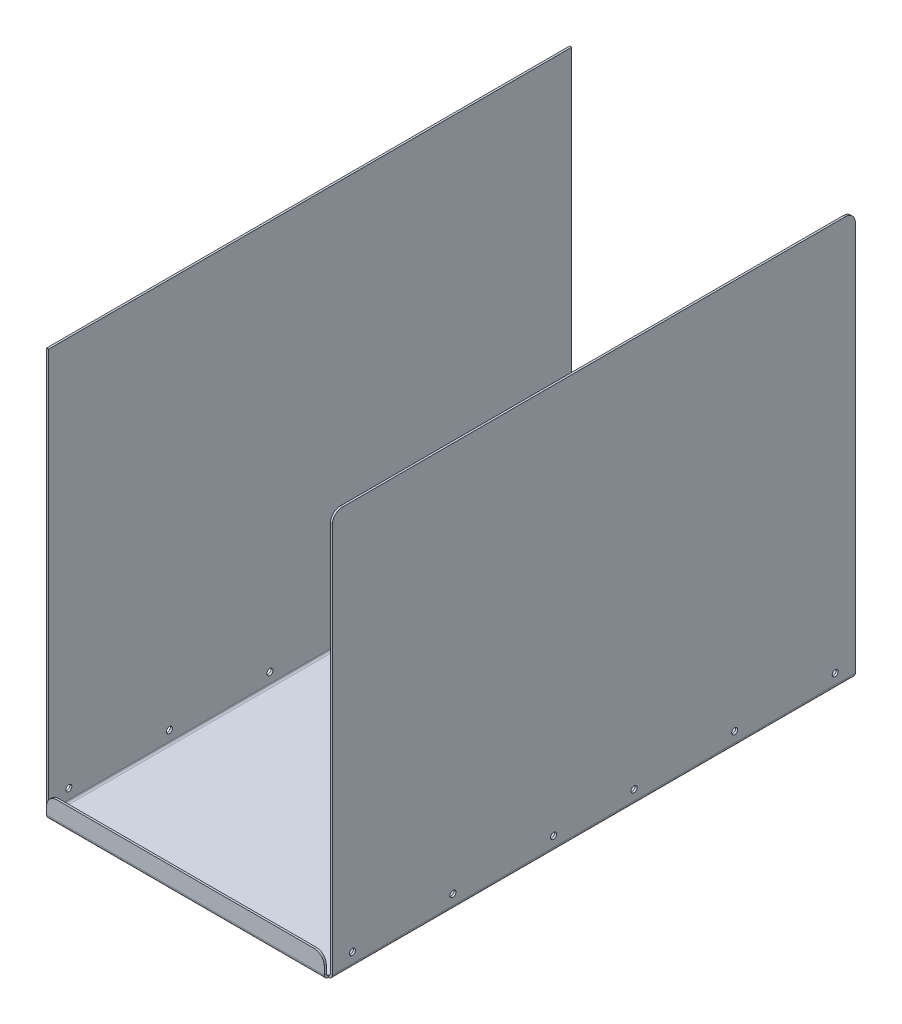
SolidWorks part; units mm, degrees
note: The reader was unsure of these and kept them because the rebuilt part matched: flange length of "Edge-Flange1", "Edge-Flange2", "Edge-Flange4", "Edge-Flange5".
material "AISI 1020"
ref_plane "Front Plane" through (0, 0, 0) normal (0, 0, 1) x (1, 0, 0)
ref_plane "Top Plane" through (0, 0, 0) normal (0, 1, 0) x (1, 0, 0)
ref_plane "Right Plane" through (0, 0, 0) normal (1, 0, 0) x (0, 0, -1)
sketch "Sketch1" plane through (0, 0, 0) normal (0, 1, 0) x (1, 0, 0)
  line L1 (0, 0) -> (142, 0)
  line L10 (0, 0) -> (0, 260)
  line L11 (0, 260) -> (142, 260)
  line L12 (142, 0) -> (142, 260)
  point P1 (142, 3.7794)
  point P2 (0, 0)
  point P5 (0, 0)
  point P6 (0, 0)
  point P7 (0, 0)
  point P9 (0, 0)
  point P18 (0, 3.1751)
  dimension "D1" = 260
  dimension "D2" = 142
base flange "Base-Flange1" sketch "Sketch1" thickness 1 reverse thickness direction no parameters "D1"=1
edge flange "Edge-Flange1" sketch "Sketch26" flange angle 90 flange length 201 flange position material inside bend radius 1 thickness 1 relief rectangular parameters "D6"=10
bend "EdgeBend7" bend radius 1 bend angle 90 parameters "D5"=1
sketch "Sketch26" plane through (0, 0, 0) normal (-1, 0, 0) x (0, 0, 1)
  line L0 (-260, 0) -> (0, 0) construction
  line L1 (-260, 0) -> (0, 0)
  line L2 (-260, 0) -> (-260, 200)
  line L3 (-260, 200) -> (0, 200)
  line L4 (0, 200) -> (0, 0)
  dimension "D1" = 200
edge flange "Edge-Flange2" sketch "Sketch28" flange angle 90 flange length 201 flange position material inside bend radius 1 thickness 1 relief rectangular parameters "D6"=10
bend "EdgeBend8" bend radius 1 bend angle 90 parameters "D5"=2
sketch "Sketch28" plane through (142, 0, 0) normal (1, 0, 0) x (0, 0, -1)
  line L0 (0, 0) -> (260, 0) construction
  line L1 (0, 0) -> (260, 0)
  line L2 (0, 0) -> (0, 195)
  line L3 (5, 200) -> (255, 200)
  line L4 (260, 195) -> (260, 0)
  arc A0 (255, 200) -> (260, 195) centre (255, 195) cw
  arc A1 (0, 195) -> (5, 200) centre (5, 195) cw
  point P8 (0, 200)
  dimension "D2" = 5
  dimension "D1" = 200
edge flange "Edge-Flange4" sketch "Sketch30" flange angle 90 flange length 11 flange position bend outside bend radius 1 thickness 1 relief rectangular parameters "D6"=10
bend "EdgeBend9" bend radius 1 bend angle 90 parameters "D5"=3
sketch "Sketch30" plane through (0, 0, -260) normal (0, 0, -1) x (-1, 0, 0)
  line L0 (-140, 0) -> (-2, 0) construction
  line L1 (-140, 0) -> (-2, 0)
  line L2 (-140, 0) -> (-140, 5)
  line L3 (-135, 10) -> (-7, 10)
  line L4 (-2, 5) -> (-2, 0)
  arc A0 (-7, 10) -> (-2, 5) centre (-7, 5) cw
  arc A1 (-140, 5) -> (-135, 10) centre (-135, 5) cw
  dimension "D2" = 5
  dimension "D1" = 10
sketch "Sketch12" plane through (0, 0, 0) normal (-1, 0, 0) x (0, 0, 1)
  line L0 (11.607, 6) -> (3.0829, 6) construction
  line L3 (11.607, 6) -> (-277.8535, 6) construction
  line L4 (0, 1) -> (0, 200) construction
  line L8 (0, 1) -> (-260, 1) construction
  circle A0 centre (-110, 6) radius 1.5
  circle A1 centre (-60, 6) radius 1.5
  circle A2 centre (-10, 6) radius 1.5
  circle A3 centre (-150, 6) radius 1.5
  circle A4 centre (-200, 6) radius 1.5
  circle A5 centre (-250, 6) radius 1.5
  point P12 (0, 5)
  point P13 (0, 0)
  point P22 (0, 0)
  point P25 (-277.8535, 5)
  point P26 (-250, 5)
  point P27 (-200, 5)
  point P28 (-128.6786, 5)
  point P29 (3.0829, 5)
  point P30 (-110, 5)
  point P31 (0, 0)
  point P32 (11.607, 5)
  point P33 (-10, 5)
  dimension "D1" = 3
  dimension "D2" = 3
  dimension "D3" = 3
  dimension "D4" = 10
  dimension "D5" = 50
  dimension "D7" = 3
  dimension "D8" = 3
  dimension "D9" = 3
  dimension "D10" = 40
  dimension "D11" = 50
  dimension "D12" = 50
  dimension "D6" = 50
  dimension "D13" = 5
extrude "Cut-Extrude1" cut sketch "Sketch12" along direction (-1, 0, 0) on the side against the normal blind 157 normal cut yes
edge flange "Edge-Flange5" sketch "Sketch32" flange angle 90 flange length 11 flange position bend outside bend radius 1 thickness 1 relief rectangular parameters "D6"=10
bend "EdgeBend10" bend radius 1 bend angle 90 parameters "D5"=4
sketch "Sketch32" plane through (0, 0, 0) normal (0, 0, 1) x (1, 0, 0)
  line L0 (2, 0) -> (140, 0) construction
  line L1 (2, 0) -> (140, 0)
  line L2 (2, 0) -> (2, 5)
  line L3 (7, 10) -> (135, 10)
  line L4 (140, 5) -> (140, 0)
  arc A0 (135, 10) -> (140, 5) centre (135, 5) cw
  arc A1 (2, 5) -> (7, 10) centre (7, 5) cw
  dimension "D1" = 5
sketch "Bend-Lines1" [suppressed] plane through (0, 0, 0) normal (0, 1, 0) x (1, 0, 0)
sketch "Bounding-Box1" [suppressed] plane through (0, 0, 0) normal (0, 1, 0) x (1, 0, 0)
sheet metal parameters "Sheet-Metal1" thickness 1 parameters "D1"=1
flat pattern "Flat-Pattern1" [suppressed]
sketch "Bend-Lines2" plane through (0, 0, 0) normal (0, 1, 0) x (1, 0, 0)
sketch3d "Bounding-Box2" [suppressed]
  line L0 (-142, 120, 0) -> (0, 120, 0) construction
  line L1 (-142, 0, 0) -> (0, 0, 0) construction
  line L2 (-142, 120, 0) -> (-142, 0, 0) construction
  line L3 (0, 120, 0) -> (0, 0, 0) construction
sheet metal parameters "Sheet-Metal2" thickness 1 parameters "D1"=1
flat pattern "Flat-Pattern1" [suppressed]
sketch "Bend-Lines2" plane through (0, 0, 0) normal (0, 1, 0) x (1, 0, 0)
  line L0 (141.1781, 0) -> (141.1781, 120) construction
  line L1 (141.1781, 0) -> (141.1781, 120) construction
sketch3d "Bounding-Box2" [suppressed]
  line L0 (0, 120, 0) -> (151.3562, 120, 0) construction
  line L1 (0, 0, 0) -> (151.3562, 0, 0) construction
  line L2 (0, 120, 0) -> (0, 0, 0) construction
  line L3 (151.3562, 120, 0) -> (151.3562, 0, 0) construction
bend of the flat pattern "Flatten-<EdgeBend7>1"
sheet metal parameters "Sheet-Metal3" thickness 1 parameters "D1"=1
flat pattern "Flat-Pattern1" [suppressed]
sketch "Bend-Lines2" plane through (0, 0, 0) normal (0, 1, 0) x (1, 0, 0)
  line L0 (141.1781, 0) -> (141.1781, 120) construction
  line L1 (141.1781, 0) -> (141.1781, 120) construction
  line L2 (0.8219, 120) -> (0.8219, 0) construction
  line L3 (0.8219, 120) -> (0.8219, 0) construction
sketch3d "Bounding-Box2" [suppressed]
  line L0 (151.3562, 0, 0) -> (151.3562, 280, 0) construction
  line L1 (-9.3562, 0, 0) -> (-9.3562, 280, 0) construction
  line L2 (151.3562, 0, 0) -> (-9.3562, 0, 0) construction
  line L3 (151.3562, 280, 0) -> (-9.3562, 280, 0) construction
bend of the flat pattern "Flatten-<EdgeBend7>5"
bend of the flat pattern "Flatten-<EdgeBend8>1"
sheet metal parameters "Sheet-Metal4" thickness 1 parameters "D1"=1
flat pattern "Flat-Pattern1" [suppressed]
sketch "Bend-Lines2" plane through (0, 0, 0) normal (0, 1, 0) x (1, 0, 0)
  line L0 (141.1781, 0) -> (141.1781, 120) construction
  line L1 (141.1781, 0) -> (141.1781, 120) construction
  line L2 (0.8219, 120) -> (0.8219, 0) construction
  line L3 (0.8219, 120) -> (0.8219, 0) construction
  line L4 (0.8219, 260) -> (0.8219, 140) construction
  line L5 (141.1781, 140) -> (141.1781, 260) construction
  line L6 (0.8219, 260) -> (0.8219, 140) construction
  line L7 (141.1781, 140) -> (141.1781, 260) construction
sketch3d "Bounding-Box2" [suppressed]
  line L0 (138.3563, 137.9999, 0) -> (138.3562, -122, 0) construction
  line L1 (-22.3561, 138, 0) -> (-22.3562, -121.9999, 0) construction
  line L2 (138.3563, 137.9999, 0) -> (-22.3561, 138, 0) construction
  line L3 (138.3562, -122, 0) -> (-22.3562, -121.9999, 0) construction
bend of the flat pattern "Flatten-<EdgeBend7>7"
bend of the flat pattern "Flatten-<EdgeBend8>5"
bend of the flat pattern "Flatten-<EdgeBend9>4"
sheet metal parameters "Sheet-Metal6" thickness 1 parameters "D1"=1
flat pattern "Flat-Pattern1" [suppressed]
sketch "Bend-Lines2" plane through (0, 0, 0) normal (0, 1, 0) x (1, 0, 0)
  line L0 (141.1781, 0) -> (141.1781, 120) construction
  line L1 (141.1781, 0) -> (141.1781, 120) construction
  line L2 (0.8219, 120) -> (0.8219, 0) construction
  line L3 (0.8219, 120) -> (0.8219, 0) construction
  line L4 (141.1781, 160) -> (141.1781, 280) construction
  line L5 (141.1781, 160) -> (141.1781, 280) construction
  line L6 (0.8219, 280) -> (0.8219, 160) construction
  line L7 (0.8219, 280) -> (0.8219, 160) construction
sketch3d "Bounding-Box2" [suppressed]
  line L0 (151.3562, 0, 0) -> (151.3562, 280, 0) construction
  line L1 (-9.3562, 0, 0) -> (-9.3562, 280, 0) construction
  line L2 (151.3562, 0, 0) -> (-9.3562, 0, 0) construction
  line L3 (151.3562, 280, 0) -> (-9.3562, 280, 0) construction
bend of the flat pattern "Flatten-<EdgeBend7>6"
bend of the flat pattern "Flatten-<EdgeBend8>4"
bend of the flat pattern "Flatten-<EdgeBend9>1"
sheet metal parameters "Sheet-Metal7" thickness 1 parameters "D1"=1
flat pattern "Flat-Pattern1"
sketch "Bend-Lines2" plane through (0, 0, 0) normal (0, 1, 0) x (1, 0, 0)
  line L10 (2, -1.1781) -> (140, -1.1781) construction
  line L11 (140, 261.1781) -> (2, 261.1781) construction
  line L12 (141.1781, 0) -> (141.1781, 260) construction
  line L13 (0.8219, 260) -> (0.8219, 0) construction
  line L14 (2, -1.1781) -> (140, -1.1781) construction
  line L15 (140, 261.1781) -> (2, 261.1781) construction
  line L16 (141.1781, 0) -> (141.1781, 260) construction
  line L17 (0.8219, 260) -> (0.8219, 0) construction
sketch3d "Bounding-Box2" [suppressed]
  line L0 (-199.3562, 271.3562, 0) -> (341.3562, 271.3562, 0) construction
  line L1 (-199.3562, -11.3562, 0) -> (341.3562, -11.3562, 0) construction
  line L2 (-199.3562, 271.3562, 0) -> (-199.3562, -11.3562, 0) construction
  line L3 (341.3562, 271.3562, 0) -> (341.3562, -11.3562, 0) construction
bend of the flat pattern "Flatten-<EdgeBend7>3"
bend of the flat pattern "Flatten-<EdgeBend8>2"
bend of the flat pattern "Flatten-<EdgeBend9>3"
bend of the flat pattern "Flatten-<EdgeBend10>1"
